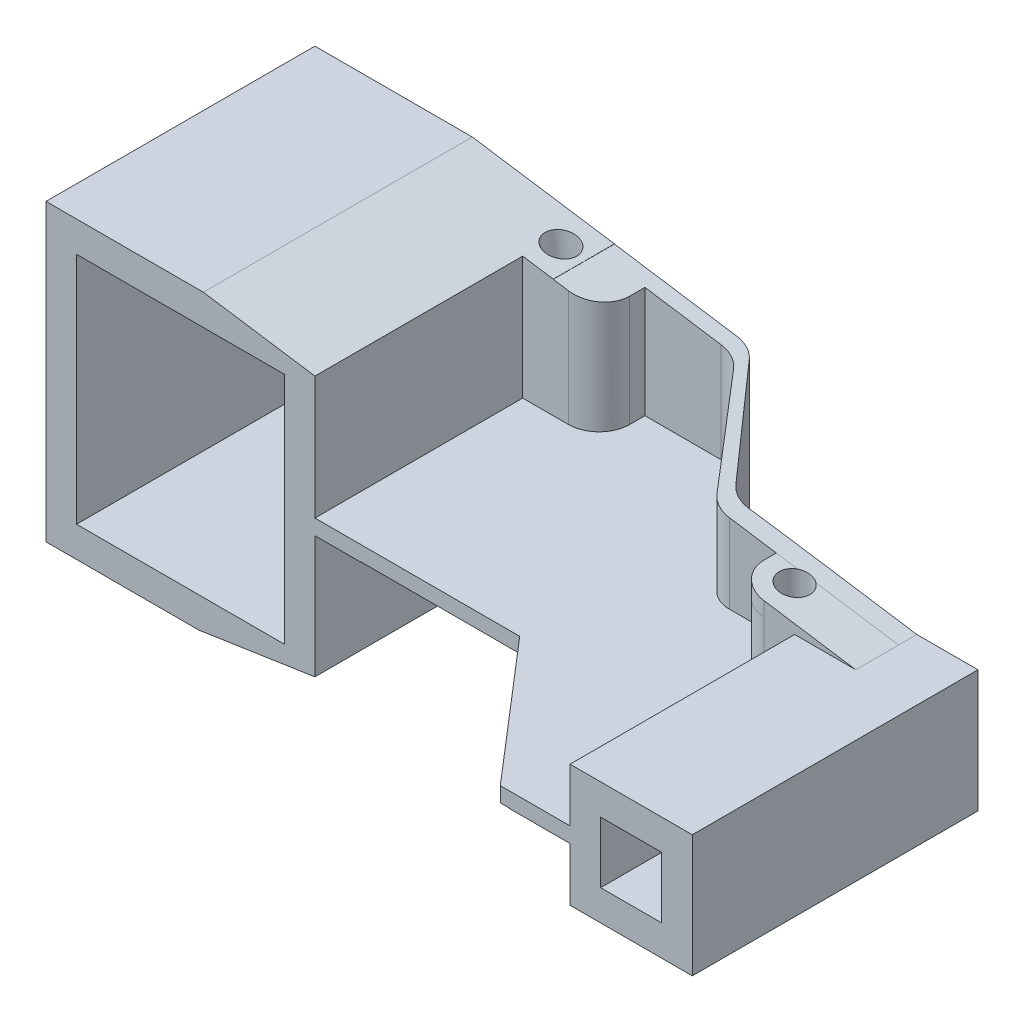
SolidWorks part; units mm, degrees
material "Alliage 1060"
ref_plane "Plan de face" through (0, 0, 0) normal (0, 0, 1) x (1, 0, 0)
ref_plane "Plan de dessus" through (0, 0, 0) normal (0, 1, 0) x (1, 0, 0)
ref_plane "Plan de droite" through (0, 0, 0) normal (1, 0, 0) x (0, 0, -1)
sketch "Esquisse1" plane through (0, 0, 0) normal (0, 0, 1) x (1, 0, 0)
  line L0 (-61.2164, -48.25) -> (125.7836, -20)
  line L18 (-101.2164, -38.25) -> (-33.2164, -38.25)
  line L20 (-101.2164, -38.25) -> (-101.2164, 38.25)
  line L21 (-101.2164, 38.25) -> (-33.2164, 38.25)
  line L22 (-33.2164, -38.25) -> (-33.2164, 38.25)
  line L23 (-101.2164, -38.25) -> (-33.2164, 38.25) construction
  line L24 (-101.2164, 38.25) -> (-33.2164, -38.25) construction
  line L25 (115.7836, -10) -> (135.7836, -10)
  line L26 (115.7836, -10) -> (115.7836, 10)
  line L27 (115.7836, 10) -> (135.7836, 10)
  line L28 (135.7836, -10) -> (135.7836, 10)
  line L29 (115.7836, -10) -> (135.7836, 10) construction
  line L30 (115.7836, 10) -> (135.7836, -10) construction
  line L31 (-111.2164, -48.25) -> (-23.2164, -48.25)
  line L32 (-111.2164, -48.25) -> (-111.2164, 48.25)
  line L33 (-111.2164, 48.25) -> (-23.2164, 48.25)
  line L34 (-23.2164, -48.25) -> (-23.2164, 48.25)
  line L35 (-111.2164, -48.25) -> (-23.2164, 48.25) construction
  line L36 (-111.2164, 48.25) -> (-23.2164, -48.25) construction
  line L37 (145.7836, -20) -> (105.7836, -20)
  line L38 (145.7836, -20) -> (145.7836, 20)
  line L39 (145.7836, 20) -> (105.7836, 20)
  line L40 (105.7836, -20) -> (105.7836, 20)
  line L41 (145.7836, -20) -> (105.7836, 20) construction
  line L42 (145.7836, 20) -> (105.7836, -20) construction
  line L43 (-61.2164, 48.25) -> (125.7836, 20)
  point P0 (-67.2164, 0)
  point P1 (125.7836, 0)
  point P2 (-67.2164, 0)
  point P7 (125.7836, 0)
  point P12 (-67.2164, 0)
  point P18 (125.7836, 0)
  point P24 (-61.2164, 48.25)
  point P26 (-61.2164, -48.25)
  dimension "D1" = 96.5
  dimension "D2" = 40
  dimension "D3" = 0
  dimension "D4" = 0
  dimension "D5" = 10
  dimension "D6" = 40
  dimension "D7" = 20
  dimension "D8" = 20
  dimension "D9" = 193
  dimension "D10" = 88
  dimension "D11" = 50
  dimension "D12" = 50
  dimension "D13" = 10
extrude "Boss.-Extru.1" add sketch "Esquisse1" along normal blind 88 contours L43 L33 L32 L31 L0 L34 L22 L18 L20 L21
sketch "Esquisse2" plane through (0, 0, 88) normal (0, 0, 1) x (1, 0, 0)
  line L0 (-59.7164, 48.25) -> (-8.2164, 40.4699)
  line L1 (-111.2164, 48.25) -> (-8.2164, 48.25)
  line L2 (-111.2164, 48.25) -> (-111.2164, -48.25)
  line L3 (-111.2164, -48.25) -> (-8.2164, -48.25)
  line L4 (-8.2164, 48.25) -> (-8.2164, -48.25)
  line L5 (-59.7164, -48.25) -> (-8.2164, -39.8179)
  line M5 (-23.2164, 42.5094) -> (-61.2164, 48.25)
  line M10 (-23.2164, -42.5094) -> (-23.2164, 42.5094)
  dimension "D1" = 96.5
  dimension "D2" = 103
extrude "Boss.-Extru.4" add sketch "Esquisse2" against normal blind 88 contours L5 L4 L0 L1 M10 M5
sketch "Esquisse3" plane through (0, 0, 88) normal (0, 0, 1) x (1, 0, 0)
  line L0 (-59.7164, 48.25) -> (-8.2164, 40.4699) construction
  line L9 (-23.2164, 42.736) -> (-3.6729, 42.736)
  line L10 (-23.2164, 42.736) -> (-23.2164, 2.5)
  line L11 (-23.2164, 2.5) -> (-3.6729, 2.5)
  line L12 (-3.6729, 42.736) -> (-3.6729, 2.5)
  line L13 (-23.2164, -2.5) -> (-2.244, -2.5)
  line L14 (-23.2164, -2.5) -> (-23.2164, -42.5094)
  line L15 (-23.2164, -42.5094) -> (-2.244, -42.5094)
  line L16 (-2.244, -2.5) -> (-2.244, -42.5094)
  point P0 (-23.2164, -42.5094)
  point P1 (-23.2164, 42.736)
  point P3 (-23.2164, 2.5)
  point P8 (-23.2164, -2.5)
extrude "Enlèv. mat.-Extru.1" cut sketch "Esquisse3" against normal blind 68 contours L10 L9 L12 L11 | L14 L13 L16 L15
sketch "Esquisse8" plane through (0, -48.25, 0) normal (0, -1, 0) x (1, 0, 0)
  line L1 (-8.2164, 20) -> (1.7836, 20)
  line L2 (-8.2164, 20) -> (-8.2164, 0)
  line L3 (-8.2164, 0) -> (1.7836, 0)
  line L4 (1.7836, 20) -> (1.7836, 0)
  dimension "D1" = 10
extrude "Boss.-Extru.9" add sketch "Esquisse8" against normal through all
sketch "Esquisse9" plane through (0, 0, 20) normal (0, 0, 1) x (1, 0, 0)
  line L0 (-43.9467, 45.8677) -> (1.7836, 38.9592)
  line L1 (-59.7164, 48.25) -> (-23.2164, 42.736) construction
  line L2 (1.7836, 48.25) -> (1.7836, -48.25) construction
  line L3 (1.7836, 38.9592) -> (1.7836, 48.25)
  line L4 (1.7836, 48.25) -> (-9.31, 48.25)
  line L5 (-9.31, 48.25) -> (-9.31, 40.6351)
  line L6 (-32.0338, -43.8414) -> (1.7836, -38.7326)
  line L7 (-61.2164, -48.25) -> (-23.2164, -42.5094) construction
  line L8 (1.7836, -38.7326) -> (1.7836, -48.25)
  line L9 (1.7836, -48.25) -> (-9.31, -48.25)
  line L10 (-9.31, -48.25) -> (-9.31, -40.4085)
  line M7 (-8.2164, -39.8179) -> (-8.2164, -48.25)
  line M8 (-8.2164, -48.25) -> (1.7836, -48.25)
  line M9 (1.7836, -48.25) -> (1.7836, 48.25)
  line M10 (1.7836, 48.25) -> (-8.2164, 48.25)
  line M11 (-8.2164, 48.25) -> (-8.2164, 40.4699)
extrude "Enlèv. mat.-Extru.2" cut sketch "Esquisse9" against normal through all contours L0 M11 M9 M10 | L6 M7 M8 M9
sketch "Esquisse10" plane through (5.7606, -38.1318, 0) normal (0.1494, -0.9888, 0) x (-0.9888, -0.1494, 0)
  line L0 (14.072, 0) -> (14.072, -20) construction
  line L1 (14.1355, 0) -> (14.1355, -20) construction
  circle A0 centre (14.1355, -10) radius 5
  point P0 (14.072, -10)
  dimension "D1" = 10.0002
extrude "Enlèv. mat.-Extru.3" cut sketch "Esquisse10" against normal through all
sketch "Esquisse17" plane through (0, 0, 20) normal (0, 0, 1) x (1, 0, 0)
  line L0 (1.7836, 38.9592) -> (1.7836, -38.7326) construction
  line L1 (-8.2164, 2.5) -> (1.7836, 2.5)
  line L2 (-8.2164, 2.5) -> (-8.2164, -2.3815)
  line L3 (-8.2164, -2.3815) -> (1.7836, -2.3815)
  line L4 (1.7836, 2.5) -> (1.7836, -2.3815)
extrude "Boss.-Extru.16" add sketch "Esquisse17" along normal through all
fillet "Congé2" radius 10 2 edges at (1.7836, 20.7296, 20) (1.7836, -20.557, 20)
sketch "Esquisse19" plane through (0, 0, 88) normal (0, 0, 1) x (1, 0, 0)
  line L0 (-101.2164, 38.25) -> (-33.2164, -38.25)
  line L1 (115.7836, -10) -> (135.7836, -10)
  line L2 (115.7836, -10) -> (115.7836, 10)
  line L3 (115.7836, 10) -> (135.7836, 10)
  line L4 (135.7836, -10) -> (135.7836, 10)
  line L5 (115.7836, -10) -> (135.7836, 10) construction
  line L6 (115.7836, 10) -> (135.7836, -10) construction
  line L7 (145.7836, -20) -> (105.7836, -20)
  line L8 (145.7836, -20) -> (145.7836, 20)
  line L9 (145.7836, 20) -> (105.7836, 20)
  line L10 (105.7836, -20) -> (105.7836, 20)
  line L11 (145.7836, -20) -> (105.7836, 20) construction
  line L12 (145.7836, 20) -> (105.7836, -20) construction
  line L13 (-33.2164, 38.25) -> (-101.2164, -38.25)
  line L14 (-101.2164, -38.25) -> (-33.2164, -38.25) construction
  point P5 (125.7836, 0)
  point P20 (-67.2164, 0)
  dimension "D1" = 193
  dimension "D2" = 40
  dimension "D3" = 40
  dimension "D4" = 10
  dimension "D5" = 10
extrude "Boss.-Extru.19" add sketch "Esquisse19" against normal blind 85 and the other way blind 56 separate body contours L10 L7 L8 L9 L4 L1 L2 L3
sketch "Esquisse20" plane through (0, -20, 0) normal (0, -1, 0) x (1, 0, 0)
  line L9 (-61.2164, 0) -> (-23.2164, 0) construction
  line L10 (104.1925, 0) -> (164.1925, 0)
  line L11 (104.1925, 0) -> (104.1925, 40)
  line L12 (104.1925, 40) -> (164.1925, 40)
  line L13 (164.1925, 0) -> (164.1925, 40)
  dimension "D1" = 40
  dimension "D2" = 60
extrude "Enlèv. mat.-Extru.4" cut sketch "Esquisse20" against normal through all
sketch "Esquisse21" plane through (0, -20, 0) normal (0, -1, 0) x (1, 0, 0)
  line L0 (105.7836, 144) -> (105.7836, 40) construction
  line L1 (145.7836, 40) -> (105.7836, 40)
  line L2 (145.7836, 40) -> (145.7836, 133.5)
  line L3 (145.7836, 133.5) -> (105.7836, 133.5)
  line L4 (105.7836, 40) -> (105.7836, 133.5)
  line L6 (105.7836, 133.5) -> (149.934, 133.5)
  line L7 (105.7836, 133.5) -> (105.7836, 153.6813)
  line L8 (105.7836, 153.6813) -> (149.934, 153.6813)
  line L9 (149.934, 133.5) -> (149.934, 153.6813)
  line M6 (145.7836, 40) -> (145.7836, 144)
  line M7 (145.7836, 144) -> (105.7836, 144)
  line M8 (105.7836, 144) -> (105.7836, 40)
  dimension "D1" = 93.5
extrude "Enlèv. mat.-Extru.5" cut sketch "Esquisse21" against normal through all contours L3 M6 M7 M8
sketch "Esquisse22" plane through (0, -20, 0) normal (0, -1, 0) x (1, 0, 0)
  line L0 (105.7836, 133.5) -> (105.7836, 40) construction
  line L1 (105.7836, 60) -> (95.7836, 60)
  line L2 (105.7836, 60) -> (105.7836, 40)
  line L3 (105.7836, 40) -> (95.7836, 40)
  line L4 (95.7836, 60) -> (95.7836, 40)
  line L5 (145.7836, 133.5) -> (145.7836, 40) construction
  line L6 (145.7836, 40) -> (105.7836, 40) construction
  point P8 (95.7836, 50)
  dimension "D1" = 50
  dimension "D2" = 20
  dimension "D3" = 0
extrude "Boss.-Extru.23" add sketch "Esquisse22" against normal blind 40
sketch "Esquisse23" plane through (0, 0, 133.5) normal (0, 0, 1) x (1, 0, 0)
  line L0 (105.7836, 20) -> (105.7836, -20) construction
  line L1 (105.7836, 2.5) -> (95.7836, 2.5)
  line L2 (105.7836, 2.5) -> (105.7836, -2.5)
  line L3 (105.7836, -2.5) -> (95.7836, -2.5)
  line L4 (95.7836, 2.5) -> (95.7836, -2.5)
  line L5 (95.7836, 20) -> (95.7836, -20) construction
  line L6 (105.7836, 20) -> (95.7836, 20) construction
  dimension "D1" = 17.5
  dimension "D2" = 17.5
  dimension "D3" = 10
extrude "Boss.-Extru.24" add sketch "Esquisse23" against normal blind 93.5
sketch "Esquisse24" plane through (0, -20, 0) normal (0, -1, 0) x (1, 0, 0)
  line L1 (95.7836, 60) -> (85.7836, 60)
  line L2 (95.7836, 60) -> (95.7836, 40)
  line L3 (95.7836, 40) -> (85.7836, 40)
  line L4 (85.7836, 60) -> (85.7836, 40)
  dimension "D1" = 10
  dimension "D2" = 20
extrude "Boss.-Extru.25" add sketch "Esquisse24" against normal blind 40
sketch "Esquisse25" plane through (0, 0, 60) normal (0, 0, 1) x (1, 0, 0)
  line L0 (85.7836, 20) -> (85.7836, -20) construction
  line L1 (95.7836, 2.5) -> (85.7836, 2.5)
  line L2 (95.7836, 2.5) -> (95.7836, -2.5)
  line L3 (95.7836, -2.5) -> (85.7836, -2.5)
  line L4 (85.7836, 2.5) -> (85.7836, -2.5)
extrude "Boss.-Extru.26" add sketch "Esquisse25" along normal blind 83.5
sketch "Esquisse26" plane through (0, -2.5, 0) normal (0, -1, 0) x (1, 0, 0)
  line L1 (95.7836, 133.5) -> (85.7836, 133.5)
  line L2 (95.7836, 133.5) -> (95.7836, 143.5)
  line L3 (95.7836, 143.5) -> (85.7836, 143.5)
  line L4 (85.7836, 133.5) -> (85.7836, 143.5)
extrude "Enlèv. mat.-Extru.6" cut sketch "Esquisse26" against normal through all
fillet "Congé3" radius 10 1 edges at (85.7836, -11.25, 60)
fillet "Congé4" radius 10 1 edges at (85.7836, 11.25, 60)
sketch "Esquisse29" plane through (0, -20, 0) normal (0, -1, 0) x (1, 0, 0)
  line L0 (1.7836, 0) -> (1.7836, 10) construction
  point P1 (1.7836, 5)
  point P2 (0, 0)
sketch "Esquisse34" plane through (0, -20, 0) normal (0, -1, 0) x (1, 0, 0)
  line L0 (1.7836, 5) -> (26.7175, 5)
  line L3 (76.7476, 46) -> (85.7836, 46)
  line L5 (85.7836, 50) -> (85.7836, 40) construction
  line L6 (145.7836, 133.5) -> (145.7836, 40) construction
  line L7 (145.7836, 46) -> (70.4467, 46)
  line L11 (62.7863, 42.4279) -> (34.3779, 8.5721)
  line L12 (145.7836, 40) -> (85.7836, 40) construction
  line L13 (1.7836, 0) -> (26.8191, 0)
  line L14 (34.3707, 3.4447) -> (62.866, 36.2708)
  line L15 (70.2336, 39.7137) -> (85.7836, 40)
  line L16 (34.3779, 8.5721) -> (34.3707, 3.4447)
  line L17 (1.7836, 5) -> (1.7836, 0)
  arc A0 (70.4467, 46) -> (62.7863, 42.4279) centre (70.4467, 36) ccw
  arc A1 (62.866, 36.2708) -> (70.2336, 39.7137) centre (70.4177, 29.7154) cw
  arc A2 (26.8191, 0) -> (34.3707, 3.4447) centre (26.8191, 10) ccw
  arc A3 (34.3779, 8.5721) -> (26.7175, 5) centre (26.7175, 15) cw
  point P3 (76.7476, 46)
  point P19 (65.7836, 46)
  dimension "D5" = 10
  dimension "D1" = 10
  dimension "D2" = 0
  dimension "D3" = 6
  dimension "D4" = 80
extrude "Boss.-Extru.30" add sketch "Esquisse34" against normal blind 59 and the other way blind 18 contours L16 A3 L0 L17 L13 A2
sketch "Esquisse35" plane through (0, 0, 40) normal (0, 0, -1) x (-1, 0, 0)
  line L0 (-145.7836, 20) -> (-85.7836, 20) construction
  line L1 (-145.7836, -20) -> (-85.7836, -20) construction
  line L2 (-145.7836, -20) -> (-145.7836, 20) construction
  line L3 (-125.7836, 20) -> (59.7164, 48.25)
  line L4 (-125.7836, -20) -> (0, -39.0021)
  line L5 (8.2164, -40.2433) -> (-1.7836, -38.7326) construction
  line L6 (-46.9149, 32.011) -> (13.2015, 41.1662)
  line L7 (13.2015, 41.1662) -> (13.2015, 63.7114)
  line L8 (13.2015, 63.7114) -> (-56.8174, 58.4838)
  line L9 (-56.8174, 58.4838) -> (-46.9149, 32.011)
  line L10 (-46.9149, -31.9147) -> (-9.7689, -63.0579)
  line L11 (-9.7689, -63.0579) -> (0, -39.0021)
  line L12 (-46.9149, -31.9147) -> (0, -39.0021)
  point P0 (-125.7836, 20)
  point P1 (-125.7836, -20)
  dimension "D1" = 20
  dimension "D2" = 20
extrude "Enlèv. mat.-Extru.9" cut sketch "Esquisse35" along normal through all contours L10 L11 L4 | L8 L9 L3 L7
sketch "Esquisse40" plane through (0, 0, 40) normal (0, 0, -1) x (-1, 0, 0)
  line L0 (-145.7836, 20) -> (-85.7836, 20) construction
  line L1 (-145.7836, -20) -> (-85.7836, -20) construction
  line L2 (-145.7836, -20) -> (-145.7836, 20) construction
  line L3 (-125.7836, 20) -> (17.9838, 41.9455)
  line L4 (59.7164, 48.25) -> (13.2015, 41.223) construction
  line L5 (-125.7836, -20) -> (27.4257, -43.1453)
  line L6 (61.2164, -48.25) -> (23.2164, -42.5094) construction
  line L7 (-125.7836, 20) -> (-85.7836, 20)
  line L8 (-85.7836, 20) -> (-85.7836, 26.1058)
  line L9 (-125.7836, -20) -> (-85.7836, -20)
  line L10 (-85.7836, -20) -> (-85.7836, -26.0428)
  point P0 (-125.7836, 20)
  point P1 (-125.7836, -20)
  line M1 (-145.7836, -20) -> (-85.7836, -20)
  line M3 (-85.7836, 20) -> (-145.7836, 20)
  dimension "D1" = 20
  dimension "D2" = 20
extrude "Boss.-Extru.33" add sketch "Esquisse40" against normal blind 20 contours L10 L5 M1 | L8 L3 M3
fillet "Congé8" radius 10 1 edges at (85.7836, 23.0529, 60)
sketch "Esquisse41" plane through (0, -20, 0) normal (0, -1, 0) x (1, 0, 0)
  circle A0 centre (95.7836, 50) radius 5
  point P1 (0, 0)
extrude "Enlèv. mat.-Extru.12" cut sketch "Esquisse41" against normal through all and the other way blind 32
sketch "Esquisse42" plane through (0, -20, 0) normal (0, -1, 0) x (1, 0, 0)
  line L2 (70.4467, 46) -> (88.6404, 46)
  line L3 (34.3779, 8.5721) -> (62.7863, 42.4279)
  line L4 (26.7175, 5) -> (6.6332, 5) construction
  line L6 (34.3707, 3.4447) -> (63.2029, 36.6589)
  line L7 (70.8237, 40.1033) -> (85.7836, 40)
  line L8 (85.7836, 46) -> (85.7836, 40)
  line L9 (34.3779, 8.5721) -> (34.3707, 3.4447)
  arc A0 (62.7863, 42.4279) -> (70.4467, 46) centre (70.4467, 36) cw
  arc A1 (63.2029, 36.6589) -> (70.8237, 40.1033) centre (70.7546, 30.1036) cw
  point P0 (82.8035, 46)
  point P11 (65.7836, 46)
  dimension "D2" = 10
  dimension "D1" = 130
extrude "Boss.-Extru.34" add sketch "Esquisse42" along normal blind 14 and the other way blind 55 contours L6 A1 L7 L8 L2 A0 L3 L9
sketch "Esquisse46" plane through (0, 0, 46) normal (0, 0, 1) x (1, 0, 0)
  line L0 (125.7836, 20) -> (1.7836, 38.8841)
  line L1 (1.7836, 38.8841) -> (91.4502, 42.4743)
  line L2 (91.4502, 42.4743) -> (125.7836, 20)
  line L3 (125.7836, -20) -> (34.3779, -34)
  line L4 (145.7836, -20) -> (105.7836, -20) construction
  line L5 (34.3779, -34) -> (1.7836, -38)
  line L6 (1.7836, -38) -> (94.8643, -42.7951)
  line L7 (94.8643, -42.7951) -> (125.7836, -20)
extrude "Enlèv. mat.-Extru.15" cut sketch "Esquisse46" against normal through all contours L2 L0 L1 | L7 L3 L5 L6
sketch "Esquisse47" plane through (0, 0, 88) normal (0, 0, 1) x (1, 0, 0)
  line L1 (1.7836, -2.3815) -> (85.7836, -2.3815)
  line L2 (1.7836, -2.3815) -> (1.7836, 2.5)
  line L3 (1.7836, 2.5) -> (85.7836, 2.5)
  line L4 (85.7836, -2.3815) -> (85.7836, 2.5)
extrude "Boss.-Extru.36" add sketch "Esquisse47" against normal up to next
sketch "Esquisse50" plane through (0, 0, 88) normal (0, 0, 1) x (1, 0, 0)
  line L0 (26.7175, -2.3815) -> (1.7836, -2.3815) construction
  line L1 (85.8959, 2.5) -> (10.7491, 2.5)
  line L2 (85.8959, 2.5) -> (85.8959, -2.3815)
  line L3 (85.8959, -2.3815) -> (10.7491, -2.3815)
  line L4 (10.7491, 2.5) -> (10.7491, -2.3815)
extrude "Boss.-Extru.38" add sketch "Esquisse50" along normal through all
sketch "Esquisse51" plane through (0, -48.25, 0) normal (0, -1, 0) x (1, 0, 0)
  line L0 (17.9144, 58.0603) -> (78.6525, 128.3062)
  line L2 (10.7491, 88) -> (43.8017, 88)
  line L3 (43.8017, 88) -> (82.9554, 133.5)
  line L4 (10.7491, 133.5) -> (85.7836, 133.5) construction
  line L5 (82.9554, 133.5) -> (10.7491, 133.5)
  line L6 (10.7491, 133.5) -> (10.7491, 88)
  point P2 (24.7152, 65.9257)
extrude "Enlèv. mat.-Extru.16" cut sketch "Esquisse51" against normal through all contours L5 L6 L2 L3
equation "\"A\"= 193"
equation "\"B\"= 88"
equation "\"W\"= 44"
equation "\"X\"=48.25"
equation "\"Y\"= 93.5"
equation "\"Z\"= 103"
equation "\"D1@Boss.-Extru.4\"=\"B\""
equation "\"D1@Enlèv. mat.-Extru.1\"=88-20"
equation "\"D1@Esquisse19\"=\"A\""
equation "\"D1@Esquisse21\"=\"Y\""
equation "\"D1@Boss.-Extru.24\"=\"Y\""
equation "\"D1@Boss.-Extru.26\"=\"Y\"-10"
